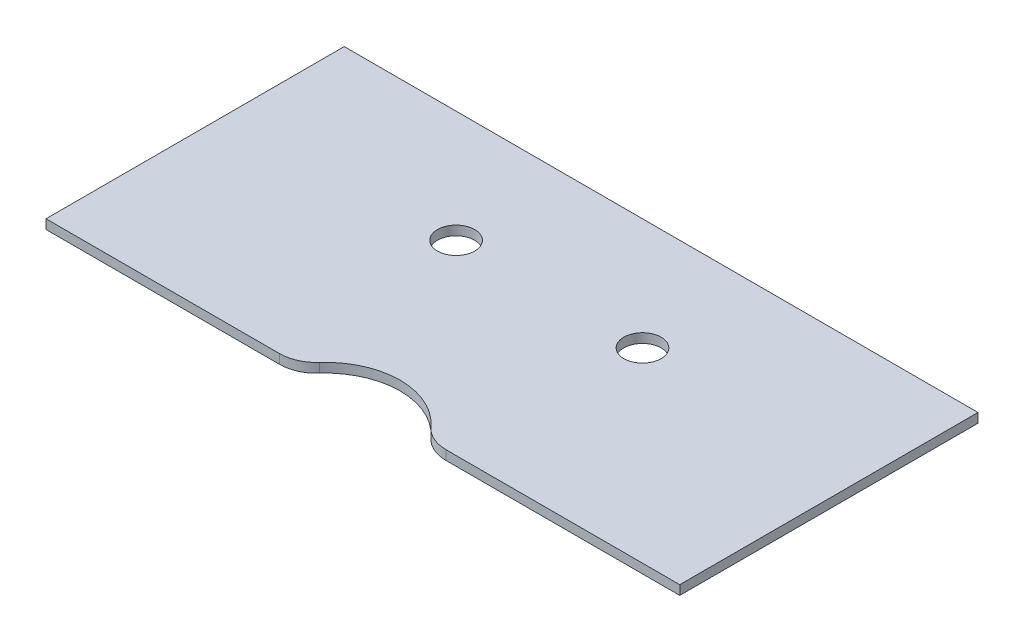
SolidWorks part; units mm, degrees
material "6061-T6 (SS)"
ref_plane "Front Plane" through (0, 0, 0) normal (0, 0, 1) x (1, 0, 0)
ref_plane "Top Plane" through (0, 0, 0) normal (0, 1, 0) x (1, 0, 0)
ref_plane "Right Plane" through (0, 0, 0) normal (1, 0, 0) x (0, 0, -1)
sketch "Sketch1" plane through (0, 0, 0) normal (0, 1, 0) x (1, 0, 0)
  line L0 (0, 101.6) -> (0, 0)
  line L1 (0, 0) -> (215.9, 0)
  line L2 (0, 0) -> (0, 228.6)
  line L3 (0, 228.6) -> (215.9, 228.6)
  line L4 (215.9, 0) -> (215.9, 228.6)
  line L5 (0, 127) -> (85.953, 127)
  line L6 (0, 127) -> (0, 101.6)
  line L7 (0, 101.6) -> (85.953, 101.6)
  line L8 (85.953, 127) -> (85.953, 101.6)
  line L9 (215.9, 127) -> (129.947, 127)
  line L10 (215.9, 127) -> (215.9, 101.6)
  line L11 (215.9, 101.6) -> (129.947, 101.6)
  line L12 (129.947, 127) -> (129.947, 101.6)
  line L13 (215.9, 0) -> (215.9, 101.6)
  circle A0 centre (107.95, 114.3) radius 25.4
  point P13 (85.953, 114.3)
  point P18 (0, 114.3)
  dimension "D4" = 50.8
  dimension "D5" = 85.953
  dimension "D1" = 228.6
  dimension "D2" = 215.9
  dimension "D3" = 25.4
extrude "Boss-Extrude1" add sketch "Sketch1" along normal blind 3.175 contours A0 L9 L4 L3 L2 L5 region at (107.95, 0, -178.6387)
sketch "Sketch2" plane through (0, 3.175, 0) normal (0, 1, 0) x (1, 0, 0)
  line L0 (0, 190.5) -> (76.2, 190.5) construction
  line L2 (76.2, 190.5) -> (139.7, 190.5) construction
  line L3 (0, 228.6) -> (215.9, 228.6) construction
  line L4 (215.9, 127) -> (215.9, 228.6) construction
  line L5 (139.7, 190.5) -> (215.9, 190.5) construction
  line L8 (0, 127) -> (0, 228.6) construction
  circle A0 centre (76.2, 190.5) radius 6.35
  circle A1 centre (139.7, 190.5) radius 6.35
  dimension "D1" = 12.7
  dimension "D2" = 38.1
  dimension "D3" = 63.5
extrude "Cut-Extrude1" cut sketch "Sketch2" against normal through all
fillet "Fillet1" radius 12.7 2 edges at (129.947, 1.5875, -127) (85.953, 1.5875, -127)
